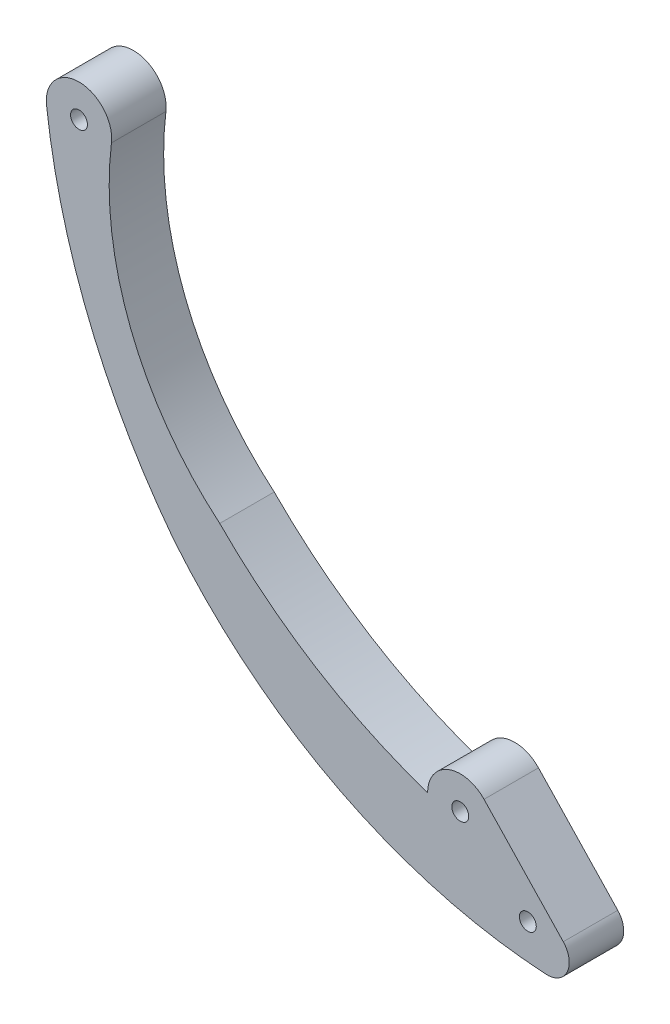
SolidWorks part; units mm, degrees
ref_plane "Plan de face" through (0, 0, 0) normal (0, 0, 1) x (1, 0, 0)
ref_plane "Plan de dessus" through (0, 0, 0) normal (0, 1, 0) x (1, 0, 0)
ref_plane "Plan de droite" through (0, 0, 0) normal (1, 0, 0) x (0, 0, -1)
sketch "Sketch2" plane through (0, 0, 0) normal (0, 0, 1) x (1, 0, 0)
  line L18 (2.9055, 2.7492) -> (-11.6417, 18.1238)
  line L19 (0, 0) -> (0, 14) construction
  line L20 (-16, 14) -> (0, 14) construction
  line L21 (-16, 14) -> (-16, 89) construction
  line L22 (-86, 89) -> (-16, 89) construction
  line L23 (0, 0) -> (0, 2.7054) construction
  line L24 (-3.6022, 2.7054) -> (0, 2.7054) construction
  arc A7 (-0.2326, -3.9932) -> (2.9055, 2.7492) centre (0, 0) ccw
  arc A8 (-11.6417, 18.1238) -> (-22, 14) centre (-16, 14) ccw
  arc A10 (-80.0437, 88.2774) -> (-91.9574, 88.286) centre (-86, 89) ccw
  arc A11 (-91.9574, 88.286) -> (-68.6302, 30.946) centre (24.4862, 102.2428) ccw
  arc A12 (-0.2326, -3.9932) -> (-68.6302, 30.946) centre (5.3171, 91.2888) cw
  circle A13 centre (-86, 89) radius 1.55
  circle A14 centre (-16, 14) radius 1.55
  arc A16 (-80.0437, 88.2774) -> (-60.1634, 37.7239) centre (-23.325, 81.3964) ccw
  arc A17 (-22, 14) -> (-60.1634, 37.7239) centre (8.7491, 106.0223) cw
  circle A18 centre (-3.6022, 2.7054) radius 1.55
  point P21 (-60.1634, 37.7239)
  point P23 (-80.0437, 88.286)
  point P24 (-22, 14)
  dimension "D5" = 16
  dimension "D6" = 75
  dimension "D7" = 70
  dimension "D8" = 3.1
  dimension "D1" = 8
  dimension "D2" = 12
  dimension "D3" = 12
  dimension "D9" = 3.1
  dimension "D10" = 3.1
  dimension "D4" = 14
  dimension "D11" = 2.7054
  dimension "D12" = 3.6022
extrude "Boss-Extrude1" add sketch "Sketch2" against normal blind 5 and the other way blind 5
